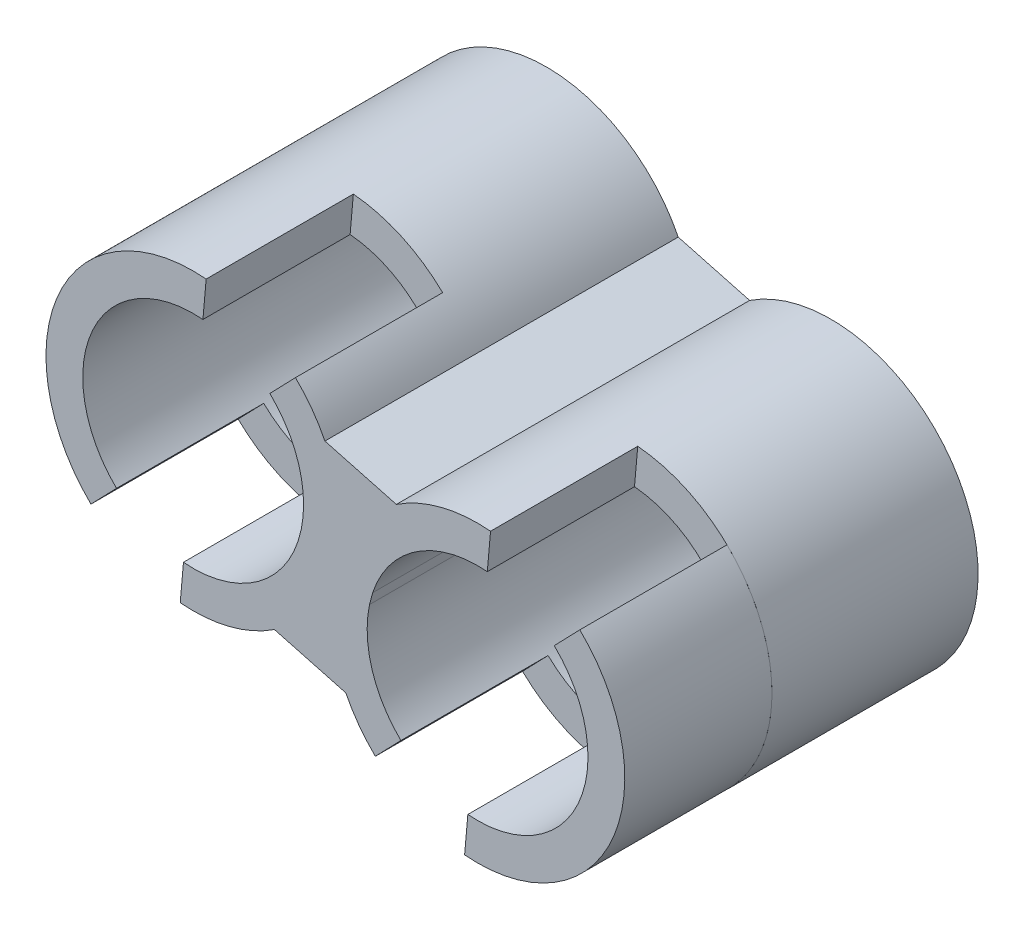
SolidWorks part; units mm, degrees
ref_plane "Front Plane" through (0, 0, 0) normal (0, 0, 1) x (1, 0, 0)
ref_plane "Top Plane" through (0, 0, 0) normal (0, 1, 0) x (1, 0, 0)
ref_plane "Right Plane" through (0, 0, 0) normal (1, 0, 0) x (0, 0, -1)
sketch "Sketch1" plane through (0, 0, 0) normal (0, 0, 1) x (1, 0, 0)
  circle A0 centre (0, 0) radius 3.285
  circle A1 centre (0, 0) radius 10
  circle A2 centre (0, 0) radius 7.5
  circle A3 centre (19.3185, -5.1764) radius 3.285
  circle A4 centre (19.3185, -5.1764) radius 10
  circle A5 centre (19.3185, -5.1764) radius 7.5
  dimension "D1" = 6.57
  dimension "D2" = 20
  dimension "D3" = 15
  dimension "D4" = 2
extrude "Boss-Extrude1" add sketch "Sketch1" along normal blind 2 contours A2 A0 | A4 | A5 A3 region at (-7.2879, 0, 0) region at (12.0306, -5.1764, 0)
extrude "Boss-Extrude2" add sketch "Sketch1<3>" along normal blind 14 contours A1 A2 | A4 A5 region at (9.634, -1.2683, 0) region at (20.5869, 4.4576, 0)
sketch "Sketch1<3>" plane through (0, 0, 0) normal (0, 0, 1) x (1, 0, 0) same geometry as "Sketch1"
sketch "Sketch2" plane through (0, 0, 14) normal (0, 0, 1) x (1, 0, 0)
  line L0 (-6.946, -7.194) -> (-5.2095, -5.3955)
  line L1 (5.2095, 5.3955) -> (6.946, 7.194)
  line L2 (0.6605, 7.4709) -> (0.8807, 9.9611)
  line L3 (-0.6605, -7.4709) -> (-0.8807, -9.9611)
  line L4 (0.6605, 7.4709) -> (5.2095, 5.3955) construction
  line L5 (-5.2095, -5.3955) -> (-0.6605, -7.4709) construction
  line L6 (12.3725, -12.3704) -> (14.109, -10.5719)
  line L7 (24.528, 0.2191) -> (26.2645, 2.0176)
  line L8 (19.9791, 2.2945) -> (20.1992, 4.7848)
  line L9 (18.658, -12.6472) -> (18.4378, -15.1375)
  line L10 (19.9791, 2.2945) -> (24.528, 0.2191) construction
  line L11 (14.109, -10.5719) -> (18.658, -12.6472) construction
  circle A0 centre (0, 0) radius 10 construction
  circle A1 centre (0, 0) radius 7.5 construction
  circle A2 centre (0, 0) radius 10
  circle A3 centre (0, 0) radius 7.5
  circle A4 centre (19.3185, -5.1764) radius 10
  circle A5 centre (19.3185, -5.1764) radius 7.5
  circle M1 centre (0, 0) radius 7.5
  circle M2 centre (0, 0) radius 10
  dimension "D1" = 5
  dimension "D2" = 5
  dimension "D3" = 2
extrude "Boss-Extrude3" add sketch "Sketch2" along normal blind 10 contours L2 L0 M1 M2 | L3 L1 M1 M2 | A5 L8 A4 L6 | A5 L9 A4 L7 region at (-8.9128, 4.0663, 14) region at (13.7032, 2.851, 14) region at (-0.5679, -8.7339, 14) region at (28.3361, -1.3482, 14)
sketch "Sketch4" plane through (0, 0, 24) normal (0, 0, 1) x (1, 0, 0)
  line L0 (13.8007, 3.1635) -> (8.9485, 4.4637)
  line L1 (8.9485, 4.4637) -> (5.5178, -8.3399)
  line L2 (5.5178, -8.3399) -> (10.37, -9.64)
  line L3 (10.37, -9.64) -> (13.8007, 3.1635)
  arc A0 (20.1992, 4.7848) -> (12.3725, -12.3704) centre (19.3185, -5.1764) ccw construction
  arc A1 (-0.8807, -9.9611) -> (6.946, 7.194) centre (0, 0) ccw construction
  point P0 (13.8007, 3.1635)
  point P1 (8.9485, 4.4637)
  point P5 (5.5178, -8.3399)
  point P9 (10.37, -9.64)
extrude "Boss-Extrude4" add sketch "Sketch4" against normal blind 24
